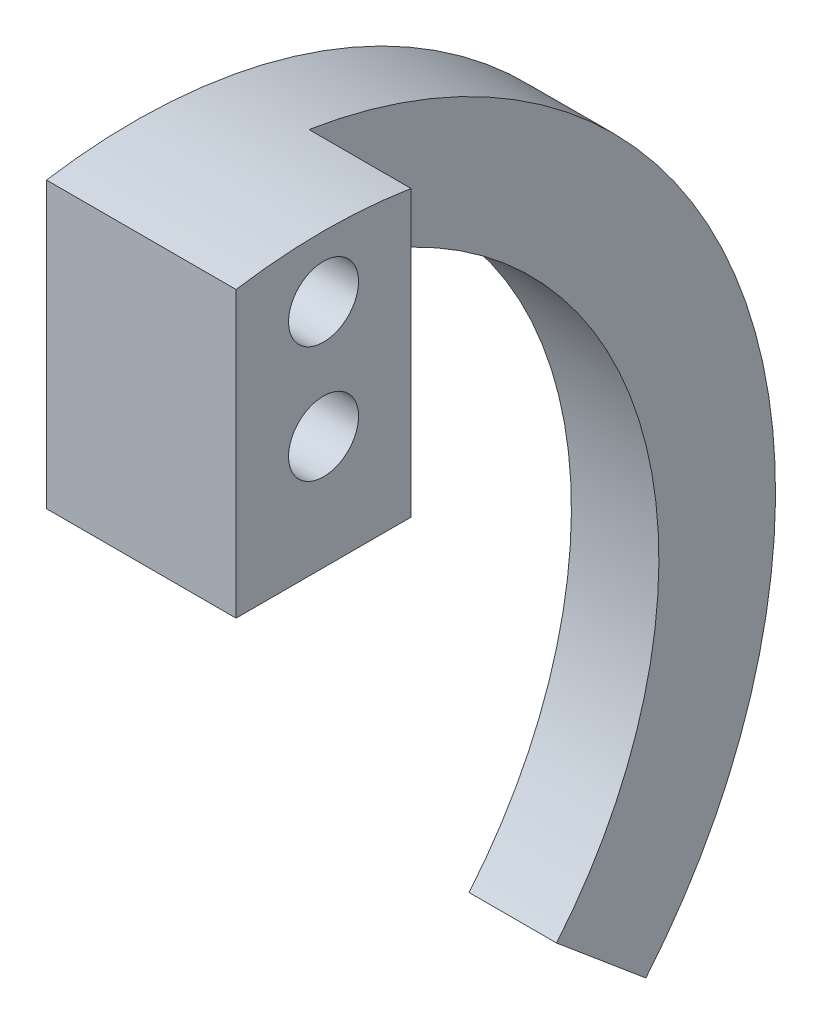
SolidWorks part; units mm, degrees
ref_plane "Alzado" through (0, 0, 0) normal (0, 0, 1) x (1, 0, 0)
ref_plane "Planta" through (0, 0, 0) normal (0, 1, 0) x (1, 0, 0)
ref_plane "Vista lateral" through (0, 0, 0) normal (1, 0, 0) x (0, 0, -1)
sketch "Croquis1" plane through (0, 0, 0) normal (1, 0, 0) x (0, 0, -1)
  line L0 (0, 0) -> (0, 8.45) construction
  line L1 (-1.5, 4.5) -> (1.5, 4.5)
  line L2 (1.5, 4.5) -> (1.5, 7.3485)
  line L4 (-1.5, 4.5) -> (-1.5, 9.3808)
  line L5 (0, 0) -> (7.2774, -6.1065) construction
  line L6 (0, 0) -> (9.5, 0) construction
  line L7 (7.2774, -6.1065) -> (5.7453, -4.8209)
  circle A0 centre (0, 8.45) radius 0.6
  circle A1 centre (0, 6.45) radius 0.6
  arc A2 (5.7453, -4.8209) -> (1.5, 7.3485) centre (0, 0) ccw
  arc A3 (7.2774, -6.1065) -> (-1.5, 9.3808) centre (0, 0) ccw
  dimension "D2" = 2
  dimension "D6" = 6.45
  dimension "D7" = 19
  dimension "D1" = 1.2
  dimension "D8" = 15
  dimension "D3" = 3
  dimension "D4" = 1.5
  dimension "D5" = 4.5
  dimension "D9" = 40
extrude "Saliente-Extruir1" add sketch "Croquis1" along normal blind 1.5
sketch "Croquis2" plane through (1.5, 0, 0) normal (1, 0, 0) x (0, 0, -1)
  line L0 (-1.5, 4.5) -> (1.5, 4.5)
  line L1 (1.5, 4.5) -> (1.5, 9.3808)
  line L4 (-1.5, 9.3808) -> (-1.5, 4.5)
  circle A0 centre (0, 6.45) radius 0.6 construction
  circle A1 centre (0, 8.45) radius 0.6 construction
  circle A2 centre (0, 6.45) radius 0.6
  circle A3 centre (0, 8.45) radius 0.6
  arc A4 (1.5, 9.3808) -> (-1.5, 9.3808) centre (0, 0) ccw
  dimension "D1" = 9.5
extrude "Saliente-Extruir2" add sketch "Croquis2" along normal blind 1.75
